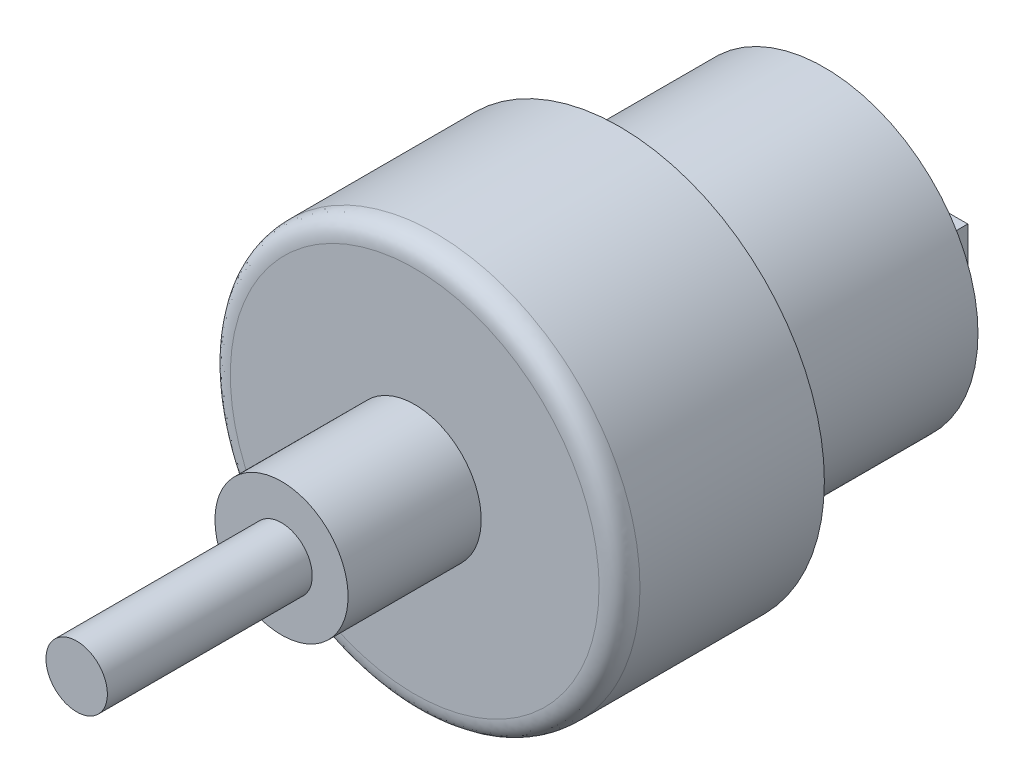
SolidWorks part; units mm, degrees
ref_plane "Front Plane" through (0, 0, 0) normal (0, 0, 1) x (1, 0, 0)
ref_plane "Top Plane" through (0, 0, 0) normal (0, 1, 0) x (1, 0, 0)
ref_plane "Right Plane" through (0, 0, 0) normal (1, 0, 0) x (0, 0, -1)
sketch "Sketch1" plane through (0, 0, 0) normal (0, 0, 1) x (1, 0, 0)
  circle A0 centre (0, 0) radius 10
  dimension "D1" = 20
extrude "Boss-Extrude1" add sketch "Sketch1" along normal blind 10
sketch "Sketch2" plane through (0, 0, 0) normal (0, 0, -1) x (-1, 0, 0)
  circle A0 centre (0, 0) radius 7.5
  dimension "D1" = 15
extrude "Boss-Extrude2" add sketch "Sketch2" along normal blind 10
sketch "Sketch3" plane through (0, 0, -10) normal (0, 0, -1) x (-1, 0, 0)
  circle A0 centre (0, 0) radius 1.5
  point P1 (0, 0)
  point P2 (0, 0)
  dimension "D1" = 3
extrude "Boss-Extrude5" add sketch "Sketch3" along normal blind 3
sketch "Sketch7" plane through (0, 0, -10) normal (0, 0, -1) x (-1, 0, 0)
  line L1 (-5.5, -2.8793) -> (-4.5, -2.8793)
  line L2 (-5.5, -2.8793) -> (-5.5, 2.8793)
  line L3 (-5.5, 2.8793) -> (-4.5, 2.8793)
  line L4 (-4.5, -2.8793) -> (-4.5, 2.8793)
  line L5 (-5.5, -2.8793) -> (-4.5, 2.8793) construction
  line L6 (-5.5, 2.8793) -> (-4.5, -2.8793) construction
  line L7 (5.5, -2.8793) -> (4.5, -2.8793)
  line L8 (5.5, -2.8793) -> (5.5, 2.8793)
  line L9 (5.5, 2.8793) -> (4.5, 2.8793)
  line L10 (4.5, -2.8793) -> (4.5, 2.8793)
  line L11 (5.5, -2.8793) -> (4.5, 2.8793) construction
  line L12 (5.5, 2.8793) -> (4.5, -2.8793) construction
  point P0 (-5, 0)
  point P5 (5, 0)
  point P10 (4.5, 0)
  dimension "D1" = 4.5
  dimension "D2" = 4.5
  dimension "D3" = 1
  dimension "D4" = 1
extrude "Boss-Extrude7" add sketch "Sketch7" along normal blind 1.5
sketch "Sketch8" plane through (0, 0, 10) normal (0, 0, 1) x (1, 0, 0)
  circle A0 centre (0, 0) radius 3.25
  dimension "D1" = 6.5
extrude "Boss-Extrude8" add sketch "Sketch8" along normal blind 6.5
sketch "Sketch9" plane through (0, 0, 16.5) normal (0, 0, 1) x (1, 0, 0)
  circle A0 centre (0, 0) radius 1.5
  dimension "D1" = 3
extrude "Boss-Extrude9" add sketch "Sketch9" along normal blind 10
fillet "Fillet2" radius 1 1 edges at (10, 0, 10) conic rho 0.5
